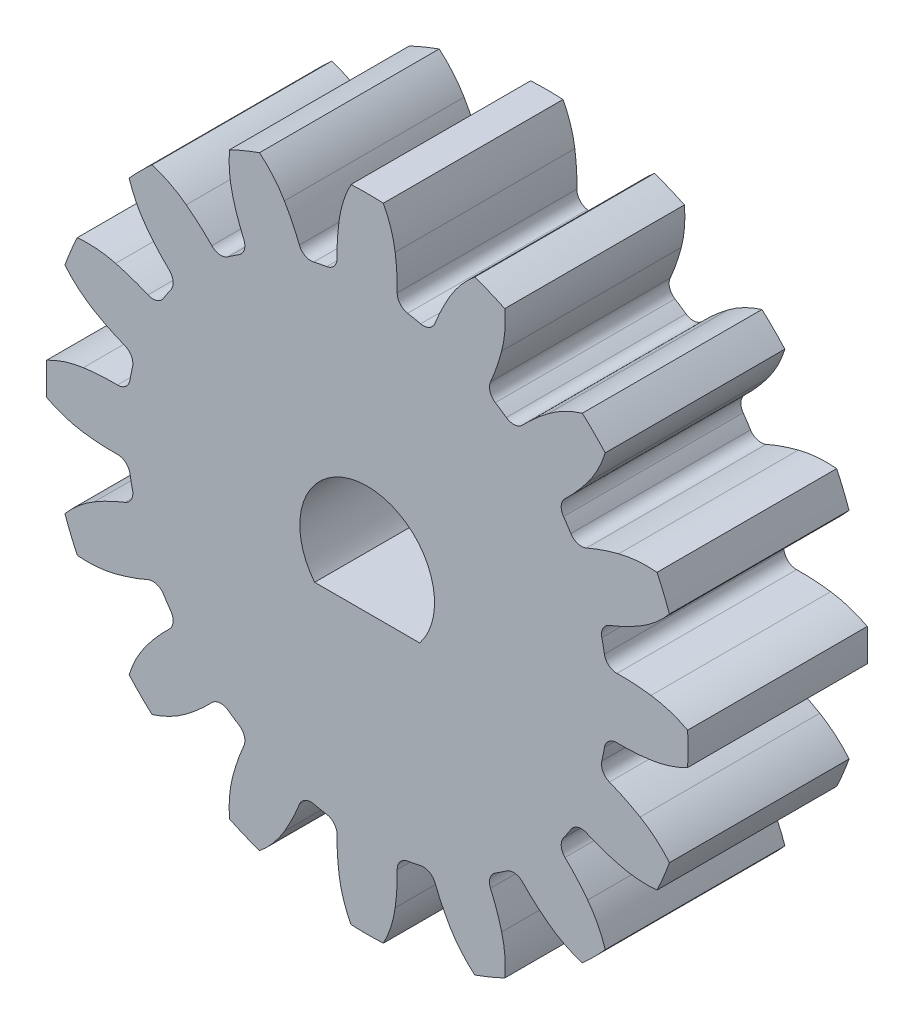
SolidWorks part; units mm, degrees
material "Plain Carbon Steel"
ref_plane "Front" through (0, 0, 0) normal (0, 0, 1) x (1, 0, 0)
ref_plane "Top" through (0, 0, 0) normal (0, 1, 0) x (1, 0, 0)
ref_plane "Right" through (0, 0, 0) normal (1, 0, 0) x (0, 0, -1)
sketch "Sketch1" plane through (0, 0, 0) normal (0, 0, 1) x (1, 0, 0)
  line L0 (0, 0) -> (6.35, 0) construction
  line L1 (6.35, 0) -> (7.1437, 0) construction
  circle A0 centre (0, 0) radius 6.35 construction
  circle A1 centre (0, 0) radius 7.1438
  dimension "pitch_diameter" = 12.7
  dimension "addendum" = 0.7937
extrude "BLANK DISK" add sketch "Sketch1" along normal mid plane 4
sketch "Sketch2" plane through (0, 0, 2) normal (0, 0, 1) x (1, 0, 0)
  line L0 (0, 0) -> (5.3578, 0) construction
  line L1 (5.3578, 0) -> (6.35, 0) construction
  line L2 (0, 0) -> (-7.1438, 0) construction
  line L3 (0, 0) -> (-6.6, -2.7338) construction
  line L4 (-6.7296, -2.3971) -> (-6.0769, -1.8423) construction
  line L5 (-6.0769, -1.8423) -> (-5.1709, -1.403) construction
  line L6 (-7.1346, -0.3607) -> (-6.3193, -0.6235) construction
  line L7 (-6.3193, -0.6235) -> (-5.3142, -0.6826) construction
  line L8 (-5.8383, -2.4183) -> (-6.0769, -1.8423) construction
  line L9 (-6.3193, -0.6235) -> (-6.3193, 0) construction
  line L12 (0, 0) -> (-6.3193, -0.6235) construction
  line L13 (0, 0) -> (-6.0769, -1.8423) construction
  line L14 (-6.0769, -1.8423) -> (-5.1274, -4.9742) construction
  line L15 (-6.3193, -0.6235) -> (-6.6407, 2.6334) construction
  line L16 (-6.0769, -1.8423) -> (-6.3193, -0.6235) construction
  line L17 (-5.2549, -1.0453) -> (-5.3142, -0.6826) construction
  line L18 (-5.2549, -1.0453) -> (-5.1709, -1.403) construction
  circle A0 centre (0, 0) radius 6.35 construction
  circle A1 centre (0, 0) radius 5.3578 construction
  circle A2 centre (0, 0) radius 7.1438 construction
  arc A3 (-6.7296, -2.3971) -> (-7.1346, -0.3607) centre (0, 0) cw
  arc A4 (-5.1709, -1.403) -> (-5.3142, -0.6826) centre (0, 0) cw construction
  arc A6 (-6.7296, -2.3971) -> (-6.0769, -1.8423) centre (-4.812, -3.9917) cw
  arc A7 (-7.1346, -0.3607) -> (-6.3193, -0.6235) centre (-5.9733, 1.8463) ccw
  arc A8 (-6.0769, -1.8423) -> (-5.3936, -1.5101) centre (-3.6467, -5.9719) cw
  arc A9 (-6.3193, -0.6235) -> (-5.561, -0.6689) centre (-5.6544, 4.1218) ccw
  arc A10 (-5.3936, -1.5101) -> (-5.2241, -1.1897) centre (-5.4949, -1.2514) ccw
  arc A11 (-5.561, -0.6689) -> (-5.2817, -0.9) centre (-5.5555, -0.9467) cw
  arc A12 (-5.2241, -1.1897) -> (-5.2817, -0.9) centre (0, 0) cw
  dimension "D12" = 2.494
  dimension "D3" = 22.5
  dimension "D4" = 0.6235
  dimension "D5" = 0.6235
  dimension "D11" = 1.2427
  dimension "D14" = 9
  dimension "D15" = 9
  dimension "base_fillet" = 0.2778
  dimension "pitch_diameter" = 12.7
  dimension "deddendum" = 0.9922
extrude "GEAR TOOTH CUT" cut sketch "Sketch2" against normal through all
ref_axis "CENTER AXIS" through (0, 0, 50) along (0, 0, -1)
pattern_circular "GEAR TEETH REVOLVE" count 16 over 360 about axis through (0, 0, 50) along (0, 0, -1) of "GEAR TOOTH CUT"
sketch "Sketch4" plane through (0, 0, 2) normal (0, 0, 1) x (1, 0, 0)
  circle A0 centre (0, 0) radius 0.75
  dimension "D1" = 1.5
extrude "Hub Extrude" add sketch "Sketch4" along normal blind 0.635
sketch "Sketch3" plane through (0, 0, 2) normal (0, 0, 1) x (1, 0, 0)
  line L0 (-1.1689, -0.94) -> (1.1689, -0.94)
  arc A0 (1.1689, -0.94) -> (-1.1689, -0.94) centre (0, 0) ccw
  dimension "D1" = 3
  dimension "D2" = 0.94
extrude "HEX BORE CUT" cut sketch "Sketch3" against normal through all and the other way through all
equation "\"N_teeth\" = 16.000000"
equation "\"pitch_diameter\" = .5000000"
equation "\"Pd\"=\"N_teeth\"/\"pitch_diameter\""
equation "\"addendum\"=1.000/\"Pd\""
equation "\"face_width\"= 4mm"
equation "\"deddendum\"=1.250/\"Pd\""
equation "\"D3@Sketch2\" = 360/\"N_teeth\""
equation "\"tooth_thickness\"=1.571/\"Pd\""
equation "\"D4@Sketch2\" = \"tooth_thickness\"/2"
equation "\"D5@Sketch2\" = \"tooth_thickness\"/2"
equation "\"Pressure_Angle\"=14.500000"
equation "\"base_fillet\"=0.35/\"Pd\""
equation "\"D12@Sketch2\" = 2*\"tooth_thickness\""
equation "\"hub_diameter\"= 1.5mm"
equation "\"bore\"= 0.125000"
equation "\"hub_projection\"=0.250000"
equation "\"sss_diam\"=0.062500"
